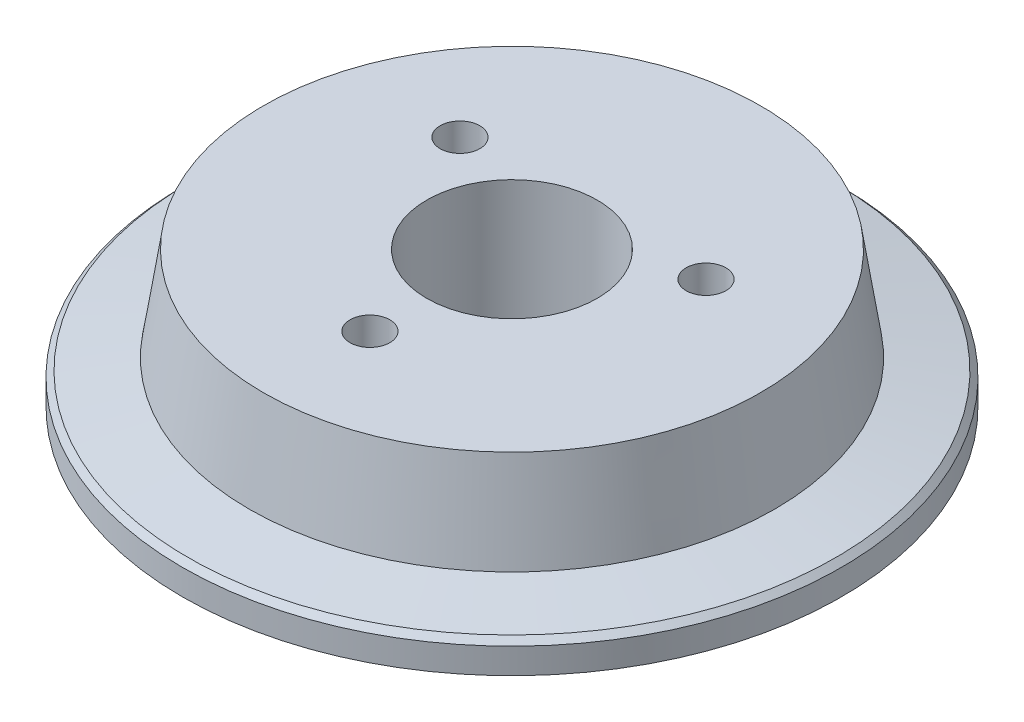
SolidWorks part; units mm, degrees
other "标注1"
sketch "草图3" plane through (-22.25, 4, -10) normal (-0.231, 0.6469, -0.7268) x (-0.9696, -0.2151, 0.1167)
ref_plane "前视基准面" through (0, 0, 0) normal (0, 0, 1) x (1, 0, 0)
ref_plane "上视基准面" through (0, 0, 0) normal (0, 1, 0) x (1, 0, 0)
ref_plane "右视基准面" through (0, 0, 0) normal (1, 0, 0) x (0, 0, -1)
other "Configuration Table"
sketch "草图4" plane through (0, 0, 0) normal (0, 1, 0) x (1, 0, 0)
  circle A0 centre (0, 0) radius 11.6
  circle A1 centre (0, 0) radius 1.1
  circle A2 centre (0, 0) radius 9.25
  dimension "D1" = 23.2
  dimension "D2" = 2.2
  dimension "D3" = 18.5
extrude "凸台-拉伸1" add sketch "草图4" along normal blind 1.1 contours A0 | A1
extrude "凸台-拉伸2" add sketch "草图4<3>" along normal blind 3.3 from offset 1.5 contours A2 | A1
sketch "草图4<3>" plane through (0, 0, 0) normal (0, 1, 0) x (1, 0, 0) same geometry as "草图4"
chamfer "倒角1" distance 0.2 angle 45 1 edges at (0, 1.1, 11.6)
loft "放样1" add section edge at (0, 1.5, 9.25) section edge at (0, 1.1, 11.4) connector at (0.6504, 1.5, 9.2271) connector at (2.6543, 1.1, 11.0867)
sketch "草图6" plane through (0, 4.8, 0) normal (0, 1, 0) x (1, 0, 0)
  circle A1 centre (0, 0) radius 3
  dimension "D2" = 6
extrude "切除-拉伸1" cut sketch "草图6" against normal through all
sketch "草图7" plane through (0, 4.8, 0) normal (0, 1, 0) x (1, 0, 0)
  circle A0 centre (0, -5) radius 0.7
  dimension "D2" = 1.4
  dimension "D1" = 5
extrude "切除-拉伸2" cut sketch "草图7" against normal blind 3
pattern_circular "阵列(圆周)1" count 3 over 360 about axis through (0, 4.8, 0) along (0, -1, 0) of "切除-拉伸2" reverse direction yes
chamfer "倒角2" distance 3.3 distance2 0.5 1 edges at (0, 4.8, 9.25) first distance on face at (0, 4.8, 9.25)
